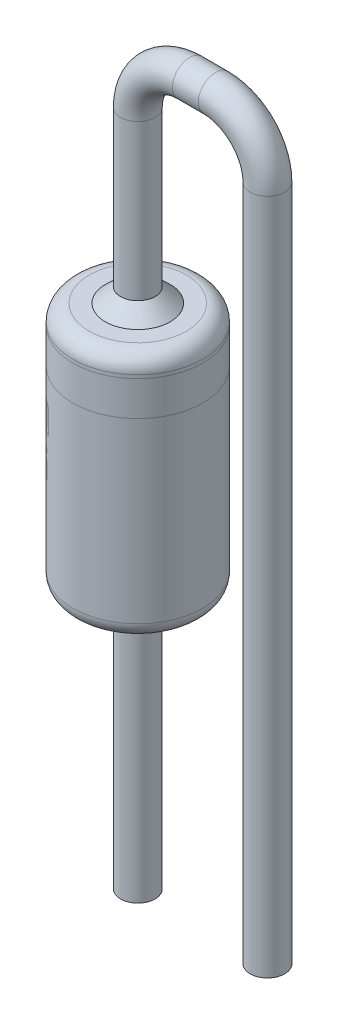
SolidWorks part; units mm, degrees
ref_plane "Front Plane" through (0, 0, 0) normal (0, 0, 1) x (1, 0, 0)
ref_plane "Top Plane" through (0, 0, 0) normal (0, 1, 0) x (1, 0, 0)
ref_plane "Right Plane" through (0, 0, 0) normal (1, 0, 0) x (0, 0, -1)
ref_plane "BODY_RPlane" through (0, 0, 0) normal (1, 0, 0) x (0, 0, -1)
sketch "Sketch10" plane through (0, 0, 0) normal (0, 0, 1) x (1, 0, 0)
  line L1 (-0.7144, 4.855) -> (-0.4763, 4.855)
  line L3 (0, 3.0325) -> (-0.9525, 3.0325) construction
  line L12 (-0.9525, 1.4481) -> (-0.9525, 4.6169)
  line L14 (-0.7076, 1.21) -> (-0.1163, 1.21) construction
  line L15 (-0.4763, 1.21) -> (-0.4763, 3.0325) construction
  line L16 (-0.7144, 1.21) -> (-0.4763, 1.21)
  line L17 (-0.4763, 1.21) -> (-0.4763, 4.855)
  line L18 (0, 1) -> (0, 5.065) construction
  arc A6 (-0.9525, 1.4481) -> (-0.7144, 1.21) centre (-0.7144, 1.4481) ccw
  arc A8 (-0.9525, 4.6169) -> (-0.7144, 4.855) centre (-0.7144, 4.6169) cw
  point P22 (0, 3.0325)
  point P30 (-0.9525, 3.0325)
  point P31 (-0.4763, 3.0325)
  point P34 (-0.9525, 3.0325)
  dimension "D8" = 0.2381
  dimension "D1" = 4.065
  dimension "D7" = 0.9525
  dimension "D9" = 0.21
  dimension "D10" = 0.4763
  dimension "D2" = 3.0325
revolve "BODY_main" add sketch "Sketch10" angle 360 about L18
sketch "Sketch11" plane through (0, 0, 0) normal (0, 0, 1) x (1, 0, 0)
  line L4 (0, 1.21) -> (0, 1)
  line L17 (-200000.7076, 1.21) -> (199999.8837, 1.21) construction
  line L18 (0, 1) -> (0, 5.065) construction
  line L19 (0, 1) -> (-0.254, 1)
  line L20 (-0.254, 1) -> (-0.4763, 1.21)
  line L21 (-0.4763, 1.21) -> (0, 1.21)
  line L22 (-0.9525, 3.0325) -> (0, 3.0325) construction
  line L23 (-0.4763, 4.855) -> (0, 4.855)
  line L24 (-0.254, 5.065) -> (-0.4763, 4.855)
  line L25 (0, 5.065) -> (-0.254, 5.065)
  line L26 (0, 4.855) -> (0, 5.065)
  dimension "D3" = 0.254
revolve "BODY_to_PIN" add sketch "Sketch11" angle 360 about L18
ref_plane "TEXT_plane" through (-1.0525, 0, 0) normal (1, 0, 0) x (0, 0, -1)
sketch "Sketch4"
  dimension "D1" = 5.9847
  dimension "D3" = 0.5081
  dimension "D5" = 0.05
  dimension "D6" = 0.15
  dimension "D2" = 5
wrap "TEXT_Wrap" sketch "Sketch4" wrap type scribe source sketch "Sketch4" face at (0.9525, 1.4481, 0)
sketch "Sketch6" plane through (1, 1, 0) normal (0, 1, 0) x (0, 0, -1)
  circle A0 centre (0, 1) radius 0.254
  dimension "D1" = 0.508
sketch "Sketch7" plane through (0, 0, 0) normal (0, 0, 1) x (1, 0, 0)
  line L0 (1.143, 8.1071) -> (0.762, 8.1071)
  line L1 (0, 7.3451) -> (0, -2.6)
  line L2 (0.9525, 8.1071) -> (0.9525, -2.6) construction
  line L3 (0, -2.6) -> (0.9525, -2.6) construction
  line L5 (0, 7.3451) -> (0, 5.065)
  line L6 (1.905, 7.3451) -> (1.905, -2.6)
  line L7 (0, -4.1102) -> (0, 4.1102) construction
  line L8 (0.254, 5.065) -> (-0.254, 5.065) construction
  arc A0 (0.762, 8.1071) -> (0, 7.3451) centre (0.762, 7.3451) ccw
  arc A1 (1.143, 8.1071) -> (1.905, 7.3451) centre (1.143, 7.3451) cw
  point P11 (0, 5.065)
  dimension "D3" = 0.762
  dimension "D1" = 2.6
sweep "PINS" add profiles "Sketch6" path "Sketch7"
equation "\"D4@Sketch7\"=\"PIN_PITCH\""
equation "\"pin_config-----------------\"= 0x000000000000000000000000000000000"
equation "\"PIN_PITCH\"= 75mil"
equation "\"PCB_standoff\"= 1mm"
equation "\"PCB_thickness\"= 1.6mm"
equation "\"PCB_bottom_lead\"= 1.0mm"
equation "\"PIN_C_max\"= 0.558mm"
equation "\"PIN_C_min\"= 0.458mm"
equation "\"body_config----------------\"= 0x000000000000000000000000000000000"
equation "\"BODY_B_max\"= 5.08mm"
equation "\"BODY_B_min\"= 3.05mm"
equation "\"BODY_D_max\"= 2.28mm"
equation "\"BODY_D_min\"= 1.53mm"
equation "\"part_config----------------\"= 0x000000000000000000000000000000000"
equation "\"Component_Size\"= 1"
equation "\"Component_Type\"= 0'variable is not used"
equation "\"D1@TEXT_plane\"=\"BODY_D\"/2 + 0.1"
equation "\"D1@Sketch4\"=\"BODY_D\" * pi"
equation "\"D1@Sketch6\"=\"PIN_C\""
equation "\"D3@Sketch7\"=\"PIN_R\""
equation "\"D1@Sketch7\"=\"PIN_L\""
equation "\"D3@Sketch4\"=\"BODY_CATM_H1\""
equation "\"D1@Sketch10\"=\"BODY_B\""
equation "\"D7@Sketch10\"=\"BODY_D\"/2"
equation "\"D8@Sketch10\"=\"BODY_D\"/8"
equation "\"D10@Sketch10\"=\"BODY_D\"/4"
equation "\"D2@Sketch10\"=\"BODY_B\"/2 + \"PCB_standoff\""
equation "\"D3@Sketch11\"=\"PIN_C\"/2"
equation "\"PIN_A_min\"= 15mm"
equation "\"auto_calc-------------------\"= 0x000000000000000000000000000000000"
equation "\"BODY_B\"= IIF ( \"Component_Size\" > 0 , IIF ( \"Component_Size\" = 1 , ( ( \"BODY_B_max\" + \"BODY_B_min\" ) / 2 ) , \"BODY_B_max\" ) , \"BODY_B_min\" )'NOT_FOR_USER , AUTOMATIC CALCULATION"
equation "\"BODY_D\"= IIF ( \"Component_Size\" > 0 , IIF ( \"Component_Size\" = 1 , ( ( \"BODY_D_max\" + \"BODY_D_min\" ) / 2 ) , \"BODY_D_max\" ) , \"BODY_D_min\" )'NOT_FOR_USER , AUTOMATIC CALCULATION"
equation "\"PIN_C\"= IIF ( \"Component_Size\" > 0 , IIF ( \"Component_Size\" = 1 , ( ( \"PIN_C_max\" + \"PIN_C_min\" ) / 2 ) , \"PIN_C_max\" ) , \"PIN_C_min\" )'NOT_FOR_USER , AUTOMATIC CALCULATION"
equation "\"PIN_L\"= \"PCB_thickness\" + \"PCB_bottom_lead\"'NOT_FOR_USER , AUTOMATIC CALCULATION"
equation "\"PIN_R\"= \"PIN_C\" * 1.5'NOT_FOR_USER , AUTOMATIC CALCULATION"
equation "\"BODY_CATM_H1\"= \"BODY_B\" / 8'NOT_FOR_USER , AUTOMATIC CALCULATION"
equation "\"D2@Sketch7\"=\"PIN_A_min\""
